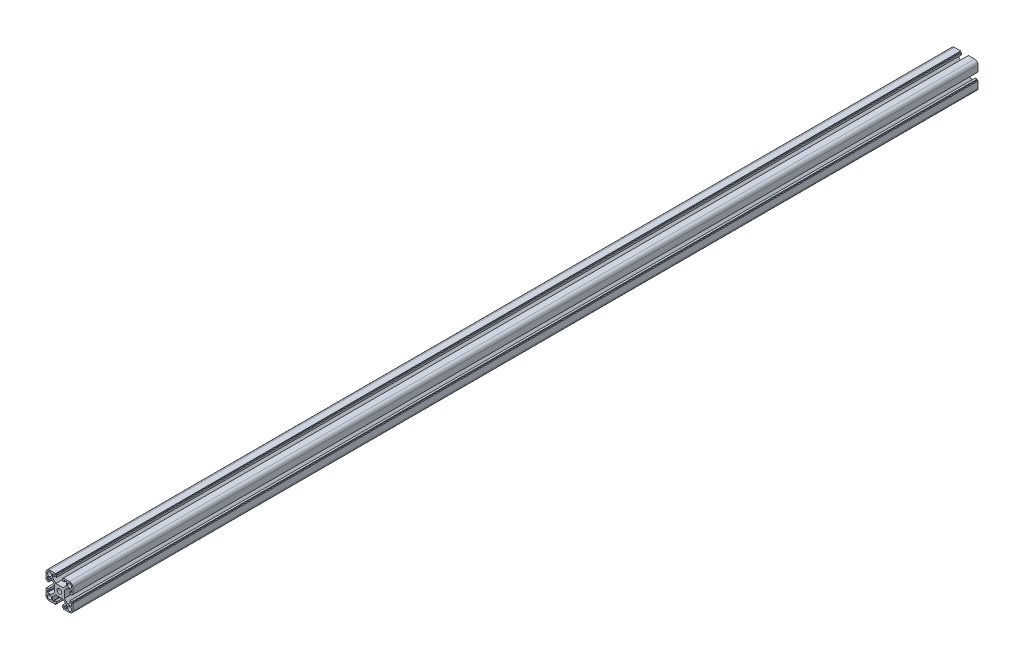
SolidWorks part; units mm, degrees
material "АД1 ГОСТ 4784-97"
ref_plane "Спереди" through (0, 0, 0) normal (0, 0, 1) x (1, 0, 0)
ref_plane "Сверху" through (0, 0, 0) normal (0, 1, 0) x (1, 0, 0)
ref_plane "Справа" through (0, 0, 0) normal (1, 0, 0) x (0, 0, -1)
ref_axis "ОсьX" through (-88.99, 0, 0) along (1, 0, 0)
ref_axis "ОсьZ" through (0, 55, 0) along (0, -1, 0)
ref_axis "ОсьY" through (0, 0, -88.99) along (0, 0, 1)
sketch "Эскиз1" plane through (0, 0, 0) normal (0, 0, 1) x (1, 0, 0)
  line L0 (-15, 20) -> (-5.7274, 20)
  line L1 (-5.7274, 20) -> (-5.7274, 18.5304)
  line L2 (-5.7274, 18.5304) -> (-4.25, 18.5304)
  line L3 (-4.25, 18.5304) -> (-4.25, 15.732)
  line L4 (-4.25, 15.732) -> (-7.1118, 15.732)
  line L5 (-7.1118, 15.732) -> (-7.1118, 17.7)
  line L6 (-7.1118, 17.7) -> (-10.5, 17.7)
  line L7 (-10.5, 17.7) -> (-10.5, 12.4799)
  line L8 (-10.5, 12.4799) -> (-5.4201, 7.4)
  line L9 (-20, 15) -> (-20, 5.7274)
  line L10 (0, 0) -> (0, 8.4096) construction
  line L11 (-15, 15) -> (0, 0) construction
  line L12 (10.5, 12.4799) -> (5.4201, 7.4)
  line L13 (10.5, 17.7) -> (10.5, 12.4799)
  line L14 (7.1118, 17.7) -> (10.5, 17.7)
  line L15 (7.1118, 15.732) -> (7.1118, 17.7)
  line L16 (4.25, 15.732) -> (7.1118, 15.732)
  line L17 (4.25, 18.5304) -> (4.25, 15.732)
  line L18 (5.7274, 18.5304) -> (4.25, 18.5304)
  line L19 (5.7274, 20) -> (5.7274, 18.5304)
  line L20 (15, 20) -> (5.7274, 20)
  line L21 (-5.4201, 7.4) -> (5.4201, 7.4)
  line L22 (-8.8445, 0) -> (0, 0) construction
  line L23 (-12.4799, 10.5) -> (-7.4, 5.4201)
  line L24 (-17.7, 10.5) -> (-12.4799, 10.5)
  line L25 (-17.7, 7.1118) -> (-17.7, 10.5)
  line L26 (-15.732, 7.1118) -> (-17.7, 7.1118)
  line L27 (-15.732, 4.25) -> (-15.732, 7.1118)
  line L28 (-18.5304, 4.25) -> (-15.732, 4.25)
  line L29 (-18.5304, 5.7274) -> (-18.5304, 4.25)
  line L30 (-20, 5.7274) -> (-18.5304, 5.7274)
  line L31 (18.5304, 5.7274) -> (18.5304, 4.25)
  line L32 (18.5304, 4.25) -> (15.732, 4.25)
  line L33 (15.732, 4.25) -> (15.732, 7.1118)
  line L34 (15.732, 7.1118) -> (17.7, 7.1118)
  line L35 (12.4799, 10.5) -> (7.4, 5.4201)
  line L36 (17.7, 10.5) -> (12.4799, 10.5)
  line L37 (17.7, 7.1118) -> (17.7, 10.5)
  line L38 (20, 5.7274) -> (18.5304, 5.7274)
  line L39 (20, 15) -> (20, 5.7274)
  line L40 (20, -15) -> (20, -5.7274)
  line L41 (20, -5.7274) -> (18.5304, -5.7274)
  line L42 (17.7, -7.1118) -> (17.7, -10.5)
  line L43 (17.7, -10.5) -> (12.4799, -10.5)
  line L44 (12.4799, -10.5) -> (7.4, -5.4201)
  line L45 (15.732, -7.1118) -> (17.7, -7.1118)
  line L46 (15.732, -4.25) -> (15.732, -7.1118)
  line L47 (18.5304, -4.25) -> (15.732, -4.25)
  line L48 (18.5304, -5.7274) -> (18.5304, -4.25)
  line L49 (-20, -5.7274) -> (-18.5304, -5.7274)
  line L50 (-18.5304, -5.7274) -> (-18.5304, -4.25)
  line L51 (-18.5304, -4.25) -> (-15.732, -4.25)
  line L52 (-15.732, -4.25) -> (-15.732, -7.1118)
  line L53 (-15.732, -7.1118) -> (-17.7, -7.1118)
  line L54 (-17.7, -7.1118) -> (-17.7, -10.5)
  line L55 (-17.7, -10.5) -> (-12.4799, -10.5)
  line L56 (-12.4799, -10.5) -> (-7.4, -5.4201)
  line L57 (-5.4201, -7.4) -> (5.4201, -7.4)
  line L58 (15, -20) -> (5.7274, -20)
  line L59 (5.7274, -20) -> (5.7274, -18.5304)
  line L60 (5.7274, -18.5304) -> (4.25, -18.5304)
  line L61 (4.25, -18.5304) -> (4.25, -15.732)
  line L62 (4.25, -15.732) -> (7.1118, -15.732)
  line L63 (7.1118, -15.732) -> (7.1118, -17.7)
  line L64 (7.1118, -17.7) -> (10.5, -17.7)
  line L65 (10.5, -17.7) -> (10.5, -12.4799)
  line L66 (10.5, -12.4799) -> (5.4201, -7.4)
  line L67 (-20, -15) -> (-20, -5.7274)
  line L68 (-10.5, -12.4799) -> (-5.4201, -7.4)
  line L69 (-10.5, -17.7) -> (-10.5, -12.4799)
  line L70 (-7.1118, -17.7) -> (-10.5, -17.7)
  line L71 (-7.1118, -15.732) -> (-7.1118, -17.7)
  line L72 (-4.25, -15.732) -> (-7.1118, -15.732)
  line L73 (-4.25, -18.5304) -> (-4.25, -15.732)
  line L74 (-5.7274, -18.5304) -> (-4.25, -18.5304)
  line L75 (-5.7274, -20) -> (-5.7274, -18.5304)
  line L76 (-15, -20) -> (-5.7274, -20)
  line L77 (-7.4, 5.4201) -> (-7.4, -5.4201)
  line L78 (7.4, 5.4201) -> (7.4, -5.4201)
  circle A0 centre (0, 0) radius 3.4
  circle A1 centre (-15, 15) radius 3.15
  arc A2 (-15, 20) -> (-20, 15) centre (-15, 15) ccw
  arc A3 (15, 20) -> (20, 15) centre (15, 15) cw
  circle A4 centre (15, 15) radius 3.15
  circle A5 centre (15, -15) radius 3.15
  arc A6 (15, -20) -> (20, -15) centre (15, -15) ccw
  arc A7 (-15, -20) -> (-20, -15) centre (-15, -15) cw
  circle A8 centre (-15, -15) radius 3.15
  dimension "D1" = 6.8
  dimension "D2" = 6.3
  dimension "D3" = 40
  dimension "D8" = 30
  dimension "D4" = 2.3
  dimension "D5" = 1.35
  dimension "D6" = 21
  dimension "D7" = 8.5
  dimension "D9" = 45
  dimension "D10" = 2.8
  dimension "D11" = 4
  dimension "D13" = 40
extrude "Бобышка-Вытянуть1" add sketch "Эскиз1" along normal mid plane 1350
